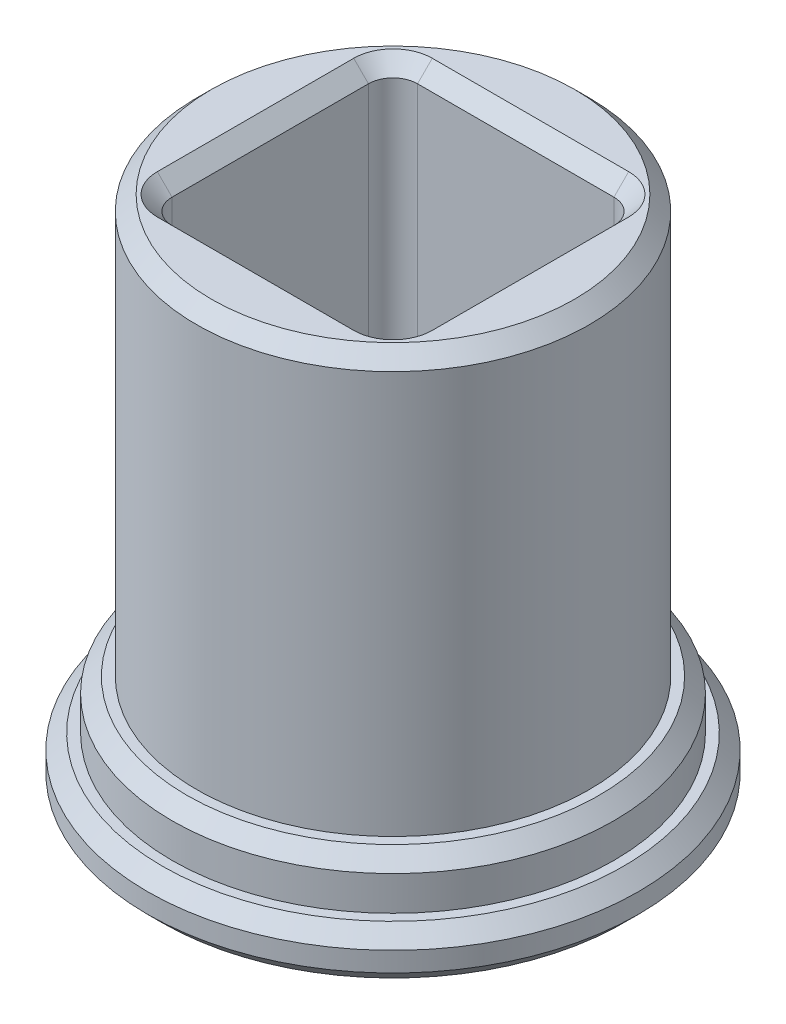
SolidWorks part; units mm, degrees
material "보통 탄소강"
ref_plane "정면" through (0, 0, 0) normal (0, 0, 1) x (1, 0, 0)
ref_plane "윗면" through (0, 0, 0) normal (0, 1, 0) x (1, 0, 0)
ref_plane "우측면" through (0, 0, 0) normal (1, 0, 0) x (0, 0, -1)
sketch "스케치1" plane through (0, 0, 0) normal (0, 1, 0) x (1, 0, 0)
  line L1 (-2.5, -2.5) -> (2.5, -2.5)
  line L2 (-2.5, -2.5) -> (-2.5, 2.5)
  line L3 (-2.5, 2.5) -> (2.5, 2.5)
  line L4 (2.5, -2.5) -> (2.5, 2.5)
  line L5 (-2.5, -2.5) -> (2.5, 2.5) construction
  line L6 (-2.5, 2.5) -> (2.5, -2.5) construction
  circle A0 centre (0, 0) radius 4
  circle A1 centre (0, 0) radius 5
  circle A2 centre (0, 0) radius 4.5
  dimension "D1" = 8
  dimension "D2" = 10
  dimension "D3" = 9
  dimension "D4" = 5
extrude "보스-돌출1" add sketch "스케치1" along normal blind 1 contours A1 A2 region at (-4.8586, 0, 0)
extrude "보스-돌출2" add sketch "스케치1<5>" along normal blind 2 contours A2 A0 region at (-4.3727, 0, 0)
sketch "스케치1<5>" plane through (0, 0, 0) normal (0, 1, 0) x (1, 0, 0) same geometry as "스케치1"
extrude "보스-돌출3" add sketch "스케치1<6>" along normal blind 10.5 contours A0 L4 L1 L2 L3 | L1 L4 L3 L2 region at (0, 0, 0) region at (-3.8869, 0, 0)
sketch "스케치1<6>" plane through (0, 0, 0) normal (0, 1, 0) x (1, 0, 0) same geometry as "스케치1"
extrude "컷-돌출1" cut sketch "스케치1<7>" against normal blind 6 from surface contours L1 L4 L3 L2 region at (0, 0, 0) starting at face at (0, 10.5, 4)
sketch "스케치1<7>" plane through (0, 0, 0) normal (0, 1, 0) x (1, 0, 0) same geometry as "스케치1"
sketch "스케치2" plane through (0, 0, 0) normal (0, -1, 0) x (1, 0, 0)
  circle A0 centre (0, 0) radius 2.2
  dimension "D1" = 4.4
extrude "컷-돌출2" cut sketch "스케치2" against normal blind 20
sketch "스케치3" plane through (0, 0, 0) normal (0, -1, 0) x (1, 0, 0)
  circle A0 centre (0, 0) radius 3.75
  dimension "D1" = 7.5
extrude "컷-돌출4" cut sketch "스케치3" against normal blind 1
fillet "필렛1" radius 0.5 4 edges at (2.5, 7.5, 2.5) (-2.5, 7.5, 2.5) (2.5, 7.5, -2.5) (-2.5, 7.5, -2.5)
chamfer "모따기1" distance 0.3 angle 45 14 edges at (0, 0, -3.75) (0, 1, -2.2) (0, 0, 5) (0, 1, 5) (0, 2, 4.5) (2.3536, 10.5, -2.3536) (2.5, 10.5, 0) (2.3536, 10.5, 2.3536) (0, 10.5, 2.5) (-2.3536, 10.5, 2.3536) (0, 10.5, -2.5) (-2.3536, 10.5, -2.3536) (-2.5, 10.5, 0) (0, 10.5, 4)
